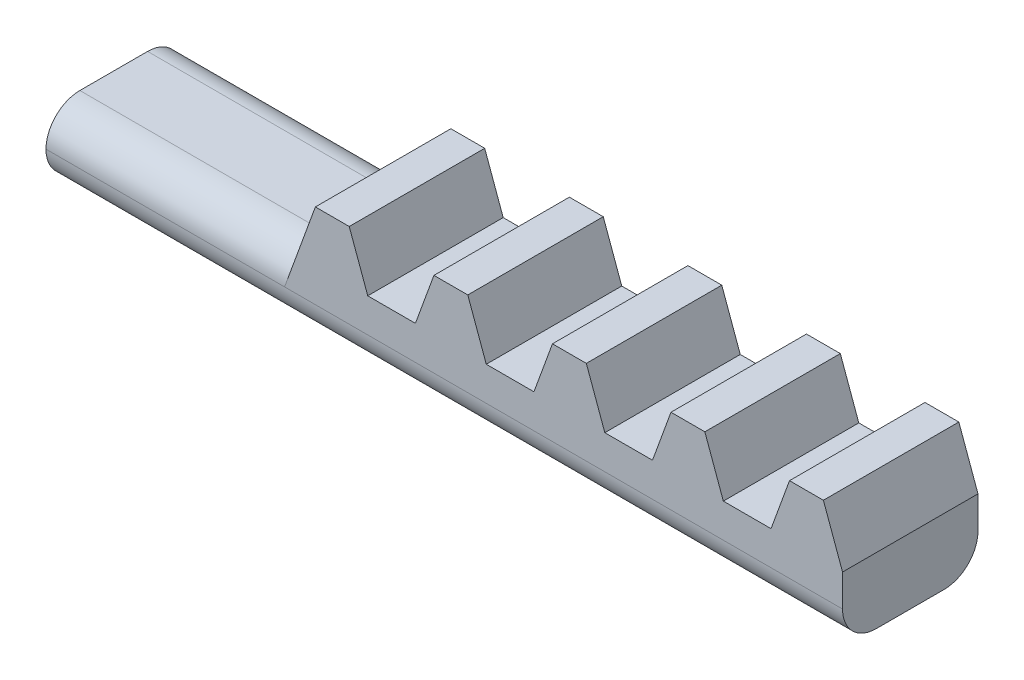
SolidWorks part; units mm, degrees
ref_plane "Front Plane" through (0, 0, 0) normal (0, 0, 1) x (1, 0, 0)
ref_plane "Top Plane" through (0, 0, 0) normal (0, 1, 0) x (1, 0, 0)
ref_plane "Right Plane" through (0, 0, 0) normal (1, 0, 0) x (0, 0, -1)
sketch "Sketch1" plane through (0, 0, 0) normal (0, 0, 1) x (1, 0, 0)
  line L0 (10, 1) -> (9.454, 2.5)
  line L1 (-10, -1) -> (10, -1)
  line L2 (-10, -1) -> (-10, 1)
  line L3 (-10, 1) -> (-2.5919, 1)
  line L5 (10, 1) -> (11.4081, 1)
  line L7 (9.454, 2.5) -> (8.454, 2.5)
  line L8 (8.454, 2.5) -> (7.9081, 1)
  line L9 (6.5, 1) -> (5.954, 2.5)
  line L10 (5.954, 2.5) -> (4.954, 2.5)
  line L11 (4.954, 2.5) -> (4.4081, 1)
  line L12 (-13.5, 1) -> (-2.5919, 1)
  line L13 (3, 1) -> (2.454, 2.5)
  line L14 (2.454, 2.5) -> (1.454, 2.5)
  line L15 (1.454, 2.5) -> (0.9081, 1)
  line L16 (-17, 1) -> (-2.5919, 1)
  line L17 (-0.5, 1) -> (-1.046, 2.5)
  line L18 (-1.046, 2.5) -> (-2.046, 2.5)
  line L19 (-2.046, 2.5) -> (-2.5919, 1)
  line L20 (-20.5, 1) -> (-2.5919, 1)
  line L21 (-0.5, 1) -> (0.9081, 1)
  line L22 (-0.5, 1) -> (0.9081, 1)
  line L23 (-0.5, 1) -> (0.9081, 1)
  line L24 (3, 1) -> (4.4081, 1)
  line L25 (3, 1) -> (4.4081, 1)
  line L26 (6.5, 1) -> (7.9081, 1)
  line L27 (11.4081, -1) -> (10, -1)
  line L28 (11.4081, 1) -> (11.954, 2.5)
  line L29 (11.954, 2.5) -> (12.954, 2.5)
  line L30 (12.954, 2.5) -> (13.5196, 0.9461)
  line L31 (13.5196, 0.9461) -> (13.5196, -1)
  line L32 (13.5196, -1) -> (11.4081, -1)
  point P0 (0, 0)
  dimension "D1" = 2
  dimension "D2" = 20
  dimension "D3" = 1
  dimension "D4" = 110
  dimension "D5" = 110
  dimension "D6" = 1.5
  dimension "D8" = 1.4081
  dimension "D9" = 1
  dimension "D10" = 1.5
  dimension "D11" = 110
  dimension "D12" = 110
  dimension "D7" = 4
extrude "Boss-Extrude1" add sketch "Sketch1" along normal blind 4 contours L26 L9 L10 L11 L24 L13 L14 L15 L21 L17 L18 L19 L3 L2 L1 L0 L7 L8 region at (2.4902, 0.3286, 0)
fillet "Fillet1" radius 1 4 edges at (1.7598, -1, 4) (1.7598, -1, 0) (-6.296, 1, 0) (-6.296, 1, 4)
